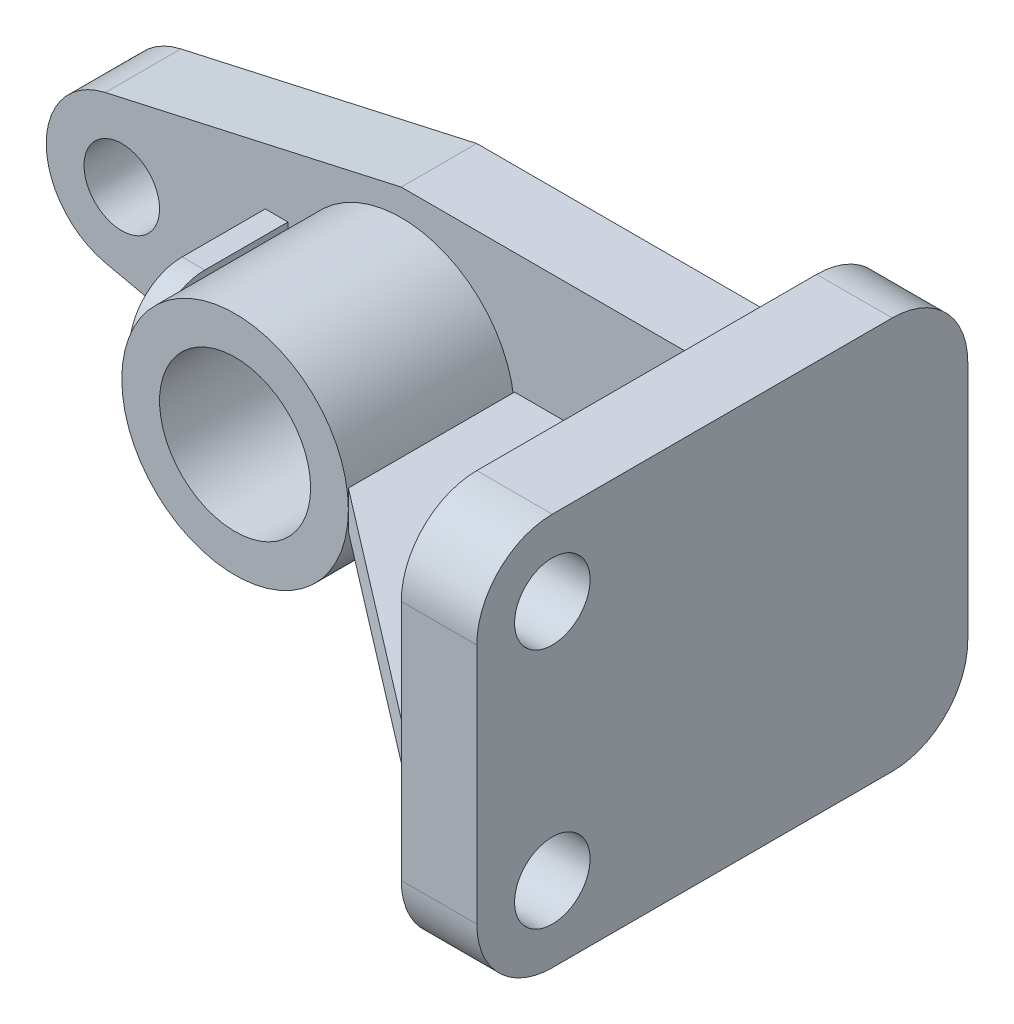
SolidWorks part; units mm, degrees
ref_plane "Front Plane" through (0, 0, 0) normal (0, 0, 1) x (1, 0, 0)
ref_plane "Top Plane" through (0, 0, 0) normal (0, 1, 0) x (1, 0, 0)
ref_plane "Right Plane" through (0, 0, 0) normal (1, 0, 0) x (0, 0, -1)
sketch "Sketch1" plane through (0, 0, 0) normal (0, 0, 1) x (1, 0, 0)
  line L0 (0, 1040.9833) -> (0, 20.4916) construction
  line L1 (-0.9292, 0) -> (-50000.9292, 0) construction
  line L2 (164, -37) -> (74, -37)
  line L8 (38, 0) -> (44, 0) construction
  line L9 (164, 52) -> (184, 52)
  line L10 (164, 52) -> (164, -52)
  line L11 (164, -52) -> (184, -52)
  line L12 (184, 52) -> (184, -52)
  line L13 (174, -52) -> (174, 52) construction
  line L14 (164, 0) -> (184, 0) construction
  line L15 (164, 37) -> (74, 37)
  line L16 (74, 37) -> (-4.3547, 19.5202)
  line L17 (74, -37) -> (-4.3547, -19.5202)
  line L18 (0, 20) -> (0, -50000) construction
  circle A0 centre (0, 0) radius 10
  circle A2 centre (74, 0) radius 20
  circle A3 centre (74, 0) radius 30
  arc A4 (-4.3547, 19.5202) -> (-4.3547, -19.5202) centre (0, 0) ccw
  point P11 (41, 0)
  point P15 (174, 0)
  point P32 (90.8168, -26.3419)
  dimension "D1" = 20
  dimension "D3" = 40
  dimension "D4" = 60
  dimension "D5" = 74
  dimension "D8" = 20
  dimension "D9" = 104
  dimension "D10" = 37
  dimension "D11" = 90
extrude "Boss-Extrude6" add sketch "Sketch1" against normal blind 20 contours L16 A4 L17 L2 L10 L15 A0 A3 region at (119, -35.0168, 0)
extrude "Boss-Extrude7" add sketch "Sketch1<7>" along normal blind 44 and the other way blind 20 separate body contours A3 A2 region at (44.8485, 0, 0)
sketch "Sketch1<7>" plane through (0, 0, 0) normal (0, 0, 1) x (1, 0, 0) same geometry as "Sketch1"
extrude "Boss-Extrude8" add sketch "Sketch1<8>" along normal blind 90 and the other way blind 40 contours L12 L9 L10 L11 region at (174, 0, 0)
sketch "Sketch1<8>" plane through (0, 0, 0) normal (0, 0, 1) x (1, 0, 0) same geometry as "Sketch1"
fillet "Fillet1" radius 20 4 edges at (174, 52, -40) (174, 52, 90) (174, -52, -40) (174, -52, 90)
hole_wizard "Ø20.0mm Dowel Hole1" positions "3DSketch1" profile "Sketch3" hole size "Ø20.0" standard "ANSI Metric"
sketch3d "3DSketch1"
  line L0 (184, 32, 70) -> (164, 32, 70) construction
  line L1 (164, -32, 70) -> (184, -32, 70) construction
  point P0 (164, 32, 70)
  point P4 (164, -32, 70)
sketch "Sketch3" plane through (164, 32, 70) normal (0, 1, 0) x (0, 0, 1)
  line L0 (0, 0) -> (0, 32)
  line L1 (0, 32) -> (10, 32)
  line L2 (10, 32) -> (10, 0)
  line L5 (10, 0) -> (0, 0)
  line L10 (0, 32) -> (-10, 32) construction
  line L11 (0, -6.35) -> (0, 107.95) construction
  dimension "Hole Dia." = 20
  dimension "Hole Depth" = 32
  dimension "Drill Angle" = 180
sketch "Sketch4" plane through (0, 0, 0) normal (0, 0, 1) x (1, 0, 0)
  line L0 (0, 0) -> (50000, 0) construction
  line L2 (38, 14) -> (44, 14)
  line L3 (38, 14) -> (38, -14)
  line L4 (38, -14) -> (44, -14)
  line L5 (44, 14) -> (44, -14)
  line L6 (41, -14) -> (41, 14) construction
  line L7 (38, 0) -> (44, 0) construction
  circle A0 centre (74, 0) radius 30 construction
  point P3 (41, 0)
  dimension "D1" = 6
  dimension "D2" = 28
extrude "Boss-Extrude9" add sketch "Sketch4" along normal blind 36
fillet "Fillet2" 2 edges at (41, -14, 36) (41, 14, 36) type full round first side face at (41, -14, 18) second side face at (41, 14, 18) middle face at (41, 0, 36)
hole_wizard "Ø16.0mm Dowel Hole1" positions "3DSketch2" profile "Sketch5" hole size "Ø16.0" standard "ANSI Metric"
sketch3d "3DSketch2"
  line L0 (38, 0, 22) -> (44, 0, 22) construction
  point P0 (38, 0, 22)
sketch "Sketch5" plane through (38, 0, 22) normal (0, 1, 0) x (0, 0, 1)
  line L0 (0, 0) -> (0, 6)
  line L1 (0, 6) -> (8, 6)
  line L2 (8, 6) -> (8, 0)
  line L5 (8, 0) -> (0, 0)
  line L10 (0, 6) -> (-8, 6) construction
  line L11 (0, -6.35) -> (0, 107.95) construction
  dimension "Hole Dia." = 16
  dimension "Hole Depth" = 6
  dimension "Drill Angle" = 180
sketch "Sketch6" plane through (0, 0, 0) normal (0, 1, 0) x (1, 0, 0)
  line L4 (164, 0) -> (164, -90)
  line L5 (164, -90) -> (104, -44)
  line L6 (104, -44) -> (104, 0)
  line L7 (104, 0) -> (164, 0)
extrude "Boss-Extrude10" add sketch "Sketch6" along normal mid plane 10
